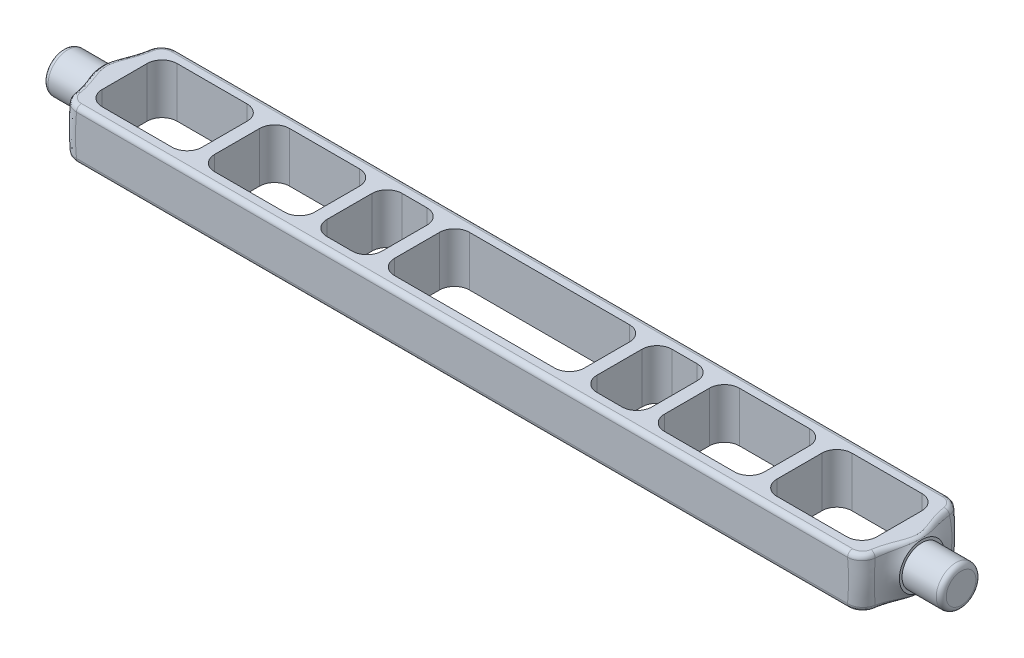
SolidWorks part; units mm, degrees
ref_plane "Front Plane" through (0, 0, 0) normal (0, 0, 1) x (1, 0, 0)
ref_plane "Top Plane" through (0, 0, 0) normal (0, 1, 0) x (1, 0, 0)
ref_plane "Right Plane" through (0, 0, 0) normal (1, 0, 0) x (0, 0, -1)
sketch "Sketch1" plane through (0, 0, 0) normal (0, 1, 0) x (1, 0, 0)
  line L1 (80, -10) -> (-80, -10)
  line L2 (80, -10) -> (80, 10)
  line L3 (80, 10) -> (-80, 10)
  line L4 (-80, -10) -> (-80, 10)
  line L5 (80, -10) -> (-80, 10) construction
  line L6 (80, 10) -> (-80, -10) construction
  point P0 (0, 0)
  dimension "D1" = 20
  dimension "D2" = 160
extrude "Boss-Extrude1" add sketch "Sketch1" along normal blind 10
sketch "Sketch2" plane through (80, 0, 0) normal (1, 0, 0) x (0, 0, -1)
  line L0 (0, 10) -> (0, 0) construction
  line L1 (-10, 10) -> (10, 10) construction
  line L2 (-10, 5) -> (10, 5) construction
  line L3 (-10, 10) -> (-10, 0) construction
  line L4 (10, 10) -> (10, 0) construction
  circle A0 centre (0, 5) radius 4.5
  dimension "D1" = 9
extrude "Boss-Extrude2" add sketch "Sketch2" along normal blind 2
fillet "Fillet1" radius 8 1 edges at (80, 5, 4.5)
sketch "Sketch3" plane through (82, 0, 0) normal (1, 0, 0) x (0, 0, -1)
  line L0 (0, 9.5) -> (0, 0.5) construction
  line L1 (-4.5, 5) -> (4.5, 5) construction
  circle A0 centre (0, 5) radius 4.5 construction
  circle A1 centre (0, 5) radius 3.9688
  dimension "D1" = 7.9375
extrude "Boss-Extrude3" add sketch "Sketch3" along normal blind 7.85
sketch "Sketch5" plane through (-80, 0, 0) normal (-1, 0, 0) x (0, 0, 1)
  line L0 (-10, 5) -> (10, 5) construction
  line L1 (-10, 10) -> (-10, 0) construction
  line L2 (10, 10) -> (10, 0) construction
  line L3 (0, 10) -> (0, 0) construction
  line L4 (-10, 10) -> (10, 10) construction
  circle A0 centre (0, 5) radius 4.5
  dimension "D1" = 9
extrude "Boss-Extrude4" add sketch "Sketch5" along normal blind 2
fillet "Fillet2" radius 8 1 edges at (-80, 5, -4.5)
sketch "Sketch6" plane through (-82, 0, 0) normal (-1, 0, 0) x (0, 0, 1)
  line L0 (-4.5, 5) -> (4.5, 5) construction
  line L1 (0, 0.5) -> (0, 9.5) construction
  circle A0 centre (0, 5) radius 4.5 construction
  circle A1 centre (0, 5) radius 3.9688
  dimension "D1" = 7.9375
extrude "Boss-Extrude5" add sketch "Sketch6" along normal blind 7.85
sketch "Sketch8" plane through (0, 10, 0) normal (0, 1, 0) x (1, 0, 0)
  line L0 (-80, -10) -> (80, -10) construction
  line L1 (-77.5, 7.5) -> (-57.5, 7.5)
  line L2 (-77.5, 7.5) -> (-77.5, -7.5)
  line L3 (-77.5, -7.5) -> (-57.5, -7.5)
  line L4 (-57.5, 7.5) -> (-57.5, -7.5)
  line L5 (-80, 10) -> (-80, 8.4186) construction
  dimension "D1" = 20
  dimension "D2" = 15
  dimension "D3" = 2.5
  dimension "D4" = 2.5
extrude "Cut-Extrude1" cut sketch "Sketch8" against normal through all
sketch "Sketch9" plane through (0, 10, 0) normal (0, 1, 0) x (1, 0, 0)
  line L0 (-80, -10) -> (80, -10) construction
  line L1 (-55, 7.5) -> (-35, 7.5)
  line L2 (-55, 7.5) -> (-55, -7.5)
  line L3 (-55, -7.5) -> (-35, -7.5)
  line L4 (-35, 7.5) -> (-35, -7.5)
  line L5 (-57.5, -7.5) -> (-57.5, 7.5) construction
  dimension "D1" = 20
  dimension "D2" = 15
  dimension "D3" = 2.5
  dimension "D4" = 2.5
extrude "Cut-Extrude2" cut sketch "Sketch9" against normal through all
fillet "Fillet3" radius 3 8 edges at (-35, 5, -7.5) (-35, 5, 7.5) (-55, 5, -7.5) (-55, 5, 7.5) (-57.5, 5, 7.5) (-57.5, 5, -7.5) (-77.5, 5, 7.5) (-77.5, 5, -7.5)
fillet "Fillet4" radius 3 2 edges at (-80, 5, -10) (-80, 5, 10)
sketch "Sketch10" plane through (0, 10, 0) normal (0, 1, 0) x (1, 0, 0)
  line L0 (-77.0645, -10) -> (80, -10) construction
  line L1 (-32.5, 7.5) -> (-21.5, 7.5)
  line L2 (-32.5, 7.5) -> (-32.5, -7.5)
  line L3 (-32.5, -7.5) -> (-21.5, -7.5)
  line L4 (-21.5, 7.5) -> (-21.5, -7.5)
  line L5 (-35, -4.5) -> (-35, 4.5) construction
  dimension "D1" = 11
  dimension "D2" = 15
  dimension "D3" = 2.5
  dimension "D4" = 2.5
extrude "Cut-Extrude3" cut sketch "Sketch10" against normal through all
sketch "Sketch11" plane through (0, 10, 0) normal (0, 1, 0) x (1, 0, 0)
  line L0 (-77.0645, -10) -> (80, -10) construction
  line L1 (-19, 7.5) -> (19, 7.5)
  line L2 (-19, 7.5) -> (-19, -7.5)
  line L3 (-19, -7.5) -> (19, -7.5)
  line L4 (19, 7.5) -> (19, -7.5)
  line L5 (-21.5, -7.5) -> (-21.5, 7.5) construction
  dimension "D1" = 38
  dimension "D2" = 15
  dimension "D3" = 2.5
  dimension "D4" = 2.5
extrude "Cut-Extrude4" cut sketch "Sketch11" against normal through all
sketch "Sketch12" plane through (0, 10, 0) normal (0, 1, 0) x (1, 0, 0)
  line L0 (-77.0645, -10) -> (80, -10) construction
  line L1 (21.5, 7.5) -> (32.5, 7.5)
  line L2 (21.5, 7.5) -> (21.5, -7.5)
  line L3 (21.5, -7.5) -> (32.5, -7.5)
  line L4 (32.5, 7.5) -> (32.5, -7.5)
  line L5 (19, -7.5) -> (19, 7.5) construction
  line L7 (35, 7.5) -> (55, 7.5)
  line L8 (35, 7.5) -> (35, -7.5)
  line L9 (35, -7.5) -> (55, -7.5)
  line L10 (55, 7.5) -> (55, -7.5)
  dimension "D1" = 11
  dimension "D2" = 15
  dimension "D3" = 2.5
  dimension "D4" = 2.5
  dimension "D5" = 20
  dimension "D6" = 15
  dimension "D7" = 2.5
  dimension "D8" = 2.5
extrude "Cut-Extrude5" cut sketch "Sketch12" against normal through all
sketch "Sketch13" plane through (0, 10, 0) normal (0, 1, 0) x (1, 0, 0)
  line L0 (-77.0645, -10) -> (80, -10) construction
  line L1 (57.5, 7.5) -> (77.5, 7.5)
  line L2 (57.5, 7.5) -> (57.5, -7.5)
  line L3 (57.5, -7.5) -> (77.5, -7.5)
  line L4 (77.5, 7.5) -> (77.5, -7.5)
  line L5 (55, -7.5) -> (55, 7.5) construction
  dimension "D1" = 20
  dimension "D2" = 15
  dimension "D3" = 2.5
  dimension "D4" = 2.5
extrude "Cut-Extrude6" cut sketch "Sketch13" against normal through all
fillet "Fillet5" radius 3 4 edges at (57.5, 5, -7.5) (35, 5, -7.5) (21.5, 5, -7.5) (-19, 5, -7.5)
fillet "Fillet6" radius 3 6 edges at (77.5, 5, -7.5) (55, 5, -7.5) (19, 5, -7.5) (-32.5, 5, -7.5) (-21.5, 5, -7.5) (32.5, 5, -7.5)
fillet "Fillet7" radius 3 5 edges at (-21.5, 5, 7.5) (19, 5, 7.5) (32.5, 5, 7.5) (55, 5, 7.5) (77.5, 5, 7.5)
fillet "Fillet8" radius 3 5 edges at (-32.5, 5, 7.5) (-19, 5, 7.5) (21.5, 5, 7.5) (35, 5, 7.5) (57.5, 5, 7.5)
fillet "Fillet9" radius 1 2 edges at (-89.85, 5, 3.9688) (89.85, 5, -3.9688)
fillet "Fillet10" radius 3 1 edges at (80, 5, 10)
fillet "Fillet11" radius 3 1 edges at (80, 5, -10)
fillet "Fillet12" radius 1 16 edges at (-79.2195, 10, 9.0917) (-78.9454, 10, -9.3402) (0, 10, -10) (79.2195, 10, -9.0917) (78.9454, 10, 9.3402) (-78.9454, 0, 9.3402) (-79.2195, 0, -9.0917) (0, 0, -10) (78.9454, 0, -9.3402) (79.2195, 0, 9.0917) (0, 10, 10) (0, 0, 10) (-81.5558, 10, 0.7158) (81.5558, 10, -0.7158) (-81.5558, 0, -0.7158) (81.5558, 0, 0.7158)
